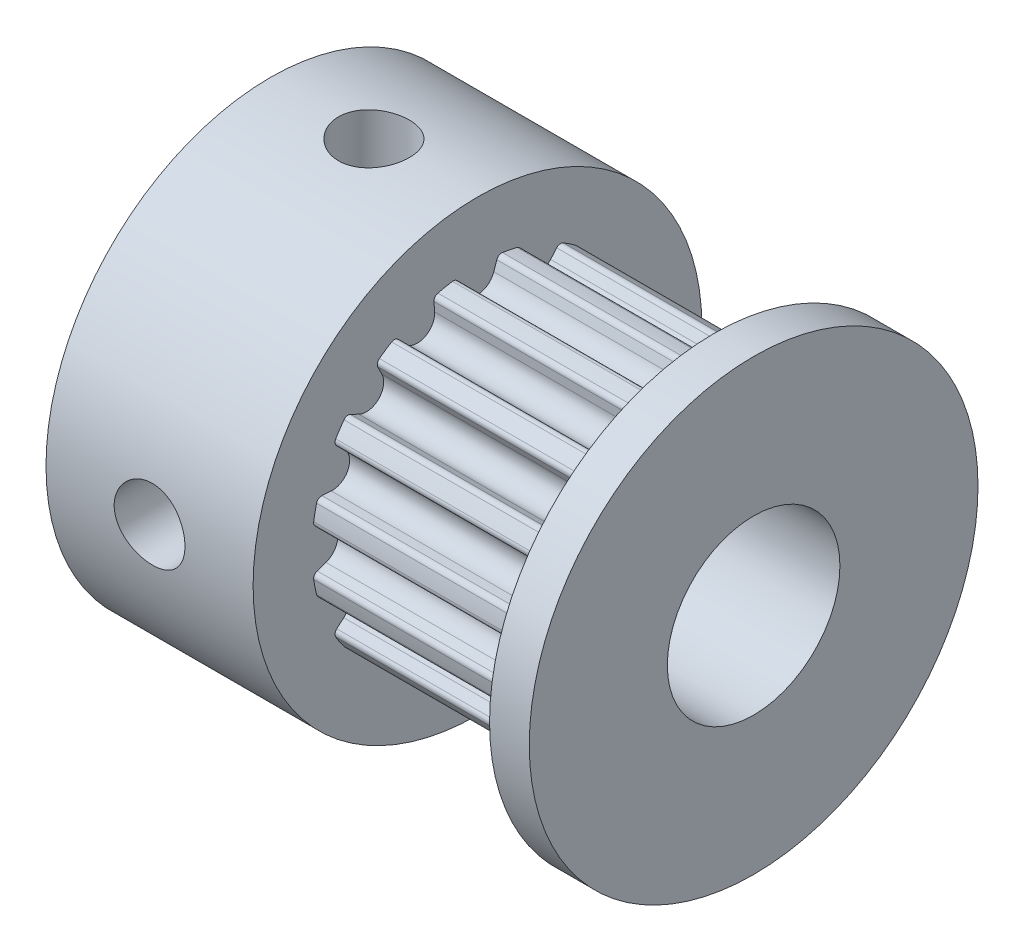
SolidWorks part; units mm, degrees
ref_plane "Alzado" through (0, 0, 0) normal (0, 0, 1) x (1, 0, 0)
ref_plane "Planta" through (0, 0, 0) normal (0, 1, 0) x (1, 0, 0)
ref_plane "Vista lateral" through (0, 0, 0) normal (1, 0, 0) x (0, 0, -1)
sketch "Croquis1" plane through (0, 0, 0) normal (1, 0, 0) x (0, 0, -1)
  circle A0 centre (0, 0) radius 6.5
  dimension "D1" = 13
extrude "Corpo Lado Motor - Ø13x6" add sketch "Croquis1" along normal blind 6
sketch "Croquis3" plane through (6, 0, 0) normal (1, 0, 0) x (0, 0, -1)
  circle A0 centre (0, 0) radius 4.8
  dimension "D1" = 9.6
extrude "Corpo dos Dentes Ø9.6x6.85" add sketch "Croquis3" along normal blind 6.85
sketch "Croquis5" plane through (6, 0, 0) normal (1, 0, 0) x (0, 0, -1)
  line L0 (0, 4.8) -> (0, 4.55) construction
  line L1 (-0.4735, 4.3894) -> (-0.6, 4.7624)
  line L2 (0.4735, 4.3894) -> (0.6, 4.7624)
  arc A1 (-0.4735, 4.3894) -> (0.4735, 4.3894) centre (0, 4.55) ccw
  arc A2 (0.6, 4.7624) -> (-0.6, 4.7624) centre (0, 0) ccw
  arc A3 (-0.6, 4.7624) -> (0.6, 4.7624) centre (0, 0) ccw construction
  circle M14 centre (0, 0) radius 4.8
  dimension "D3" = 9.6
  dimension "D1" = 0.5
  dimension "D2" = 0.75
  dimension "D4" = 1.2
extrude "Corte do Dente - R0.5" cut sketch "Croquis5" along normal up to next contours L1 A1 L2 M14 region at (6, 4.4739, 0)
fillet "Arredondamento - Raio 0.15mm" radius 0.15 2 edges at (9.425, 4.7624, -0.6) (9.425, 4.7624, 0.6)
pattern_circular "Corte dos 16 Dentes" count 16 over 360 about axis through (12.85, 0, 0) along (1, 0, 0) of "Corte do Dente - R0.5", "Arredondamento - Raio 0.15mm"
sketch "Croquis4" plane through (12.85, 0, 0) normal (1, 0, 0) x (0, 0, -1)
  circle A0 centre (0, 0) radius 6.5
  dimension "D1" = 13
extrude "Face Direita Ø20" add sketch "Croquis4" along normal blind 1.15
sketch "Croquis6" plane through (0, 0, 0) normal (-1, 0, 0) x (0, 0, 1)
  circle A0 centre (0, 0) radius 2.5
  dimension "D1" = 5
extrude "Furo Passante Ø5" cut sketch "Croquis6" against normal up to surface (14 mm away) up to face at (14, 0, -6.5)
ref_plane "Plano de Referência" through (0, 6.5, 0) normal (0, 1, 0) x (1, 0, 0)
hole_wizard "Furo de Fixação 1 - M2.5" positions "Sketch4" profile "Sketch5" tap size "M2.5x0.45" standard "ANSI Metric" end condition up to next
sketch "Sketch4" plane through (0, 6.5, 0) normal (0, 1, 0) x (1, 0, 0)
  line L0 (0, 0) -> (6, 0) construction
  line L3 (6, -6.5) -> (6, 6.5) construction
  point P0 (3, 0)
  point P10 (0, 0)
  point P11 (3, 0)
  point P12 (6, 0)
sketch "Sketch5" plane through (3, 6.5, 0) normal (1, 0, 0) x (0, 0, 1)
  line L0 (0, 0) -> (0, 4)
  line L1 (0, 4) -> (1.025, 4)
  line L2 (1.025, 4) -> (1.025, 0)
  line L5 (1.025, 0) -> (0, 0)
  line L11 (0, -6.35) -> (0, 107.95) construction
  dimension "Thru Tap Drill Dia." = 2.05
  dimension "Thru Tap Drill Depth" = 4
cosmetic thread "Hole Thread2" parameters "D2"=2.5
pattern_circular "Furo de Fixação 2 - M2.5" count 2 every 90 about axis through (21.0711, 0, 0) along (-1, 0, 0) of "Furo de Fixação 1 - M2.5" reverse direction yes
